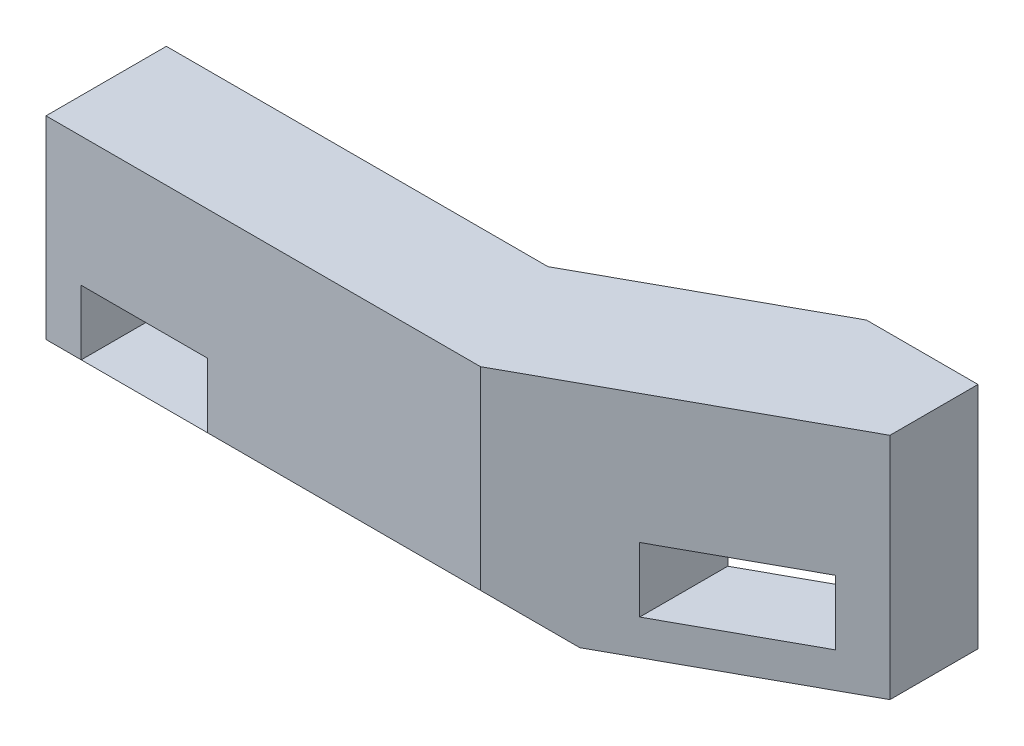
SolidWorks part; units mm, degrees
ref_plane "Front Plane" through (0, 0, 0) normal (0, 0, 1) x (1, 0, 0)
ref_plane "Top Plane" through (0, 0, 0) normal (0, 1, 0) x (1, 0, 0)
ref_plane "Right Plane" through (0, 0, 0) normal (1, 0, 0) x (0, 0, -1)
sketch "Sketch1" plane through (0, 0, 0) normal (0, 1, 0) x (1, 0, 0)
  line L0 (6.5, -2.05) -> (8.3, -2.05)
  line L1 (-6.5, -2.05) -> (6.5, -2.05)
  line L2 (-6.5, -2.05) -> (-6.5, 2.05)
  line L3 (-6.5, 2.05) -> (6.5, 2.05)
  line L4 (6.5, -2.05) -> (6.5, 2.05)
  line L5 (-6.5, -2.05) -> (6.5, 2.05) construction
  line L6 (-6.5, 2.05) -> (6.5, -2.05) construction
  line L7 (8.3, -2.05) -> (17.3, 2.8991)
  line L8 (17.3, 2.8991) -> (17.3, 5.8991)
  line L9 (6.5, 2.05) -> (13.4996, 5.8991)
  line L10 (13.4996, 5.8991) -> (17.3, 5.8991)
  point P0 (0, 0)
  point P6 (13.4996, 5.8991)
  point P11 (0, 0)
  dimension "D1" = 13
  dimension "D2" = 4.1
  dimension "D3" = 1.8
  dimension "D4" = 9
  dimension "D5" = 4.9491
  dimension "D6" = 3
extrude "Boss-Extrude1" add sketch "Sketch1" along normal mid plane 7.8 contours L10 L9 L4 L0 L7 L8 | L1 L4 L3 L2 region at (11.6578, 0, -2.2342) region at (0, 0, 0)
sketch "Sketch2" plane through (0, -3.9, 0) normal (0, -1, 0) x (1, 0, 0)
  line L0 (17.3, -5.8991) -> (8.3, -0.95)
  line L1 (8.3, -0.95) -> (6.5, -2.05)
  line L2 (8.3, 2.05) -> (17.3, -2.8991) construction
  line L3 (6.5, -2.05) -> (13.4996, -5.8991)
  line L4 (13.4996, -5.8991) -> (17.3, -5.8991)
  dimension "D1" = 0
extrude "Cut-Extrude1" cut sketch "Sketch2" against normal offset from surface (6.6 mm away) 1.2 up to face at (7.1285, 3.9, -2.0996)
sketch "Sketch3" plane through (0, 0, 2.05) normal (0, 0, 1) x (1, 0, 0)
  line L0 (-6.5, 3.9) -> (-6.5, -3.9) construction
  line L1 (-5.3, -0.5) -> (-1, -0.5)
  line L2 (-5.3, -0.5) -> (-5.3, -2.7)
  line L3 (-5.3, -2.7) -> (-1, -2.7)
  line L4 (-1, -0.5) -> (-1, -2.7)
  line L5 (-5.3, -0.5) -> (-1, -2.7) construction
  line L6 (-5.3, -2.7) -> (-1, -0.5) construction
  line L7 (-6.5, -3.9) -> (8.3, -3.9) construction
  line L8 (17.3, 3.9) -> (17.3, -3.9) construction
  line L9 (11.8, -0.5) -> (16.1, -0.5)
  line L10 (11.8, -0.5) -> (11.8, -2.7)
  line L11 (11.8, -2.7) -> (16.1, -2.7)
  line L12 (16.1, -0.5) -> (16.1, -2.7)
  line L13 (11.8, -0.5) -> (16.1, -2.7) construction
  line L14 (11.8, -2.7) -> (16.1, -0.5) construction
  line L15 (8.3, -3.9) -> (17.3, -3.9) construction
  point P0 (-3.15, -1.6)
  point P9 (13.95, -1.6)
  dimension "D1" = 2.2
  dimension "D2" = 4.3
  dimension "D3" = 1.2
  dimension "D4" = 1.2
  dimension "D5" = 4.3
  dimension "D6" = 2.2
  dimension "D7" = 1.2
  dimension "D8" = 1.2
extrude "Cut-Extrude2" cut sketch "Sketch3" against normal through all both and the other way through all
chamfer "Chamfer1" distance 1.2 angle 45 1 edges at (0.9, -3.9, 2.05)
